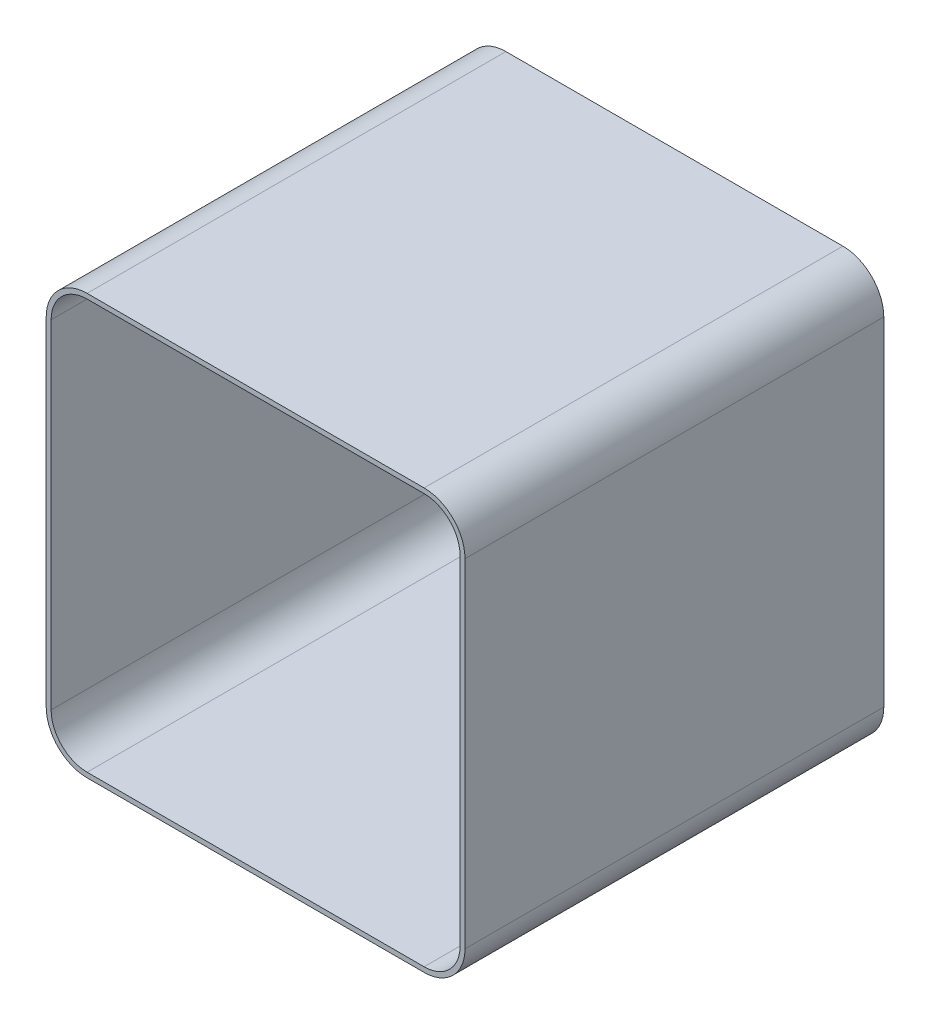
SolidWorks part; units mm, degrees
material "Pine"
ref_plane "Front Plane" through (0, 0, 0) normal (0, 0, 1) x (1, 0, 0)
ref_plane "Top Plane" through (0, 0, 0) normal (0, 1, 0) x (1, 0, 0)
ref_plane "Right Plane" through (0, 0, 0) normal (1, 0, 0) x (0, 0, -1)
sketch "Sketch1" plane through (0, 0, 0) normal (0, 0, 1) x (1, 0, 0)
  line L1 (44, 0) -> (456, 0)
  line L2 (0, 44) -> (0, 457)
  line L3 (44, 501) -> (456, 501)
  line L4 (500, 44) -> (500, 457)
  arc A0 (0, 457) -> (44, 501) centre (44, 457) cw
  arc A1 (456, 501) -> (500, 457) centre (456, 457) cw
  arc A2 (456, 0) -> (500, 44) centre (456, 44) ccw
  arc A3 (44, 0) -> (0, 44) centre (44, 44) cw
  point P5 (0, 0)
  point P6 (0, 0)
  point P9 (0, 501)
  point P12 (500, 501)
  point P15 (500, 0)
  point P18 (0, 0)
  dimension "D3" = 44
  dimension "D4" = 44
  dimension "D5" = 44
  dimension "D6" = 44
  dimension "D1" = 500
  dimension "D2" = 501
extrude "Extrude-Thin1" add sketch "Sketch1" against normal blind 512 thin contours A0 L3 A1 L4 A2 L1 A3 L2 thin type one direction wall 6
sketch "Sketch2" plane through (0, 0, 0) normal (1, 0, 0) x (0, 0, -1)
  line L0 (0, 322) -> (512, 322)
  line L1 (0, 44) -> (0, 457) construction
  line L2 (512, 457) -> (0, 457) construction
  dimension "D1" = 135
  dimension "D2" = 512
